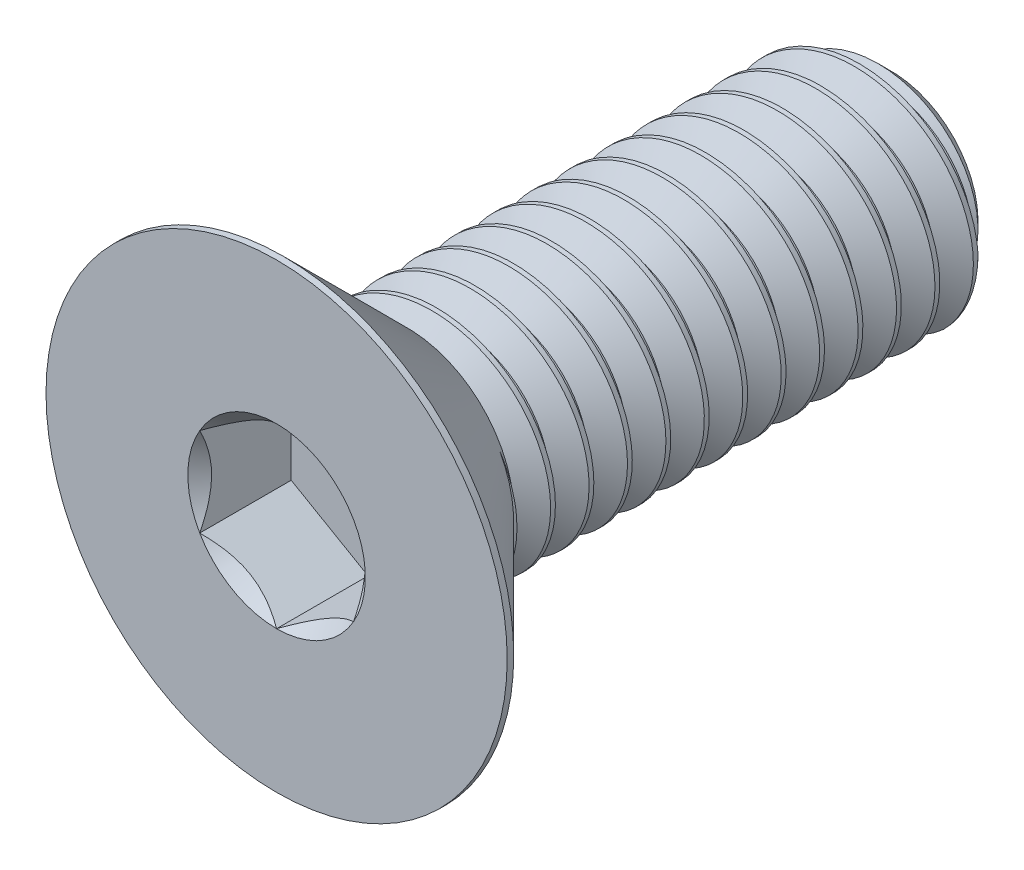
SolidWorks part; units mm, degrees
ref_plane "Front" through (0, 0, 0) normal (0, 0, 1) x (1, 0, 0)
ref_plane "Top" through (0, 0, 0) normal (0, 1, 0) x (1, 0, 0)
ref_plane "Right" through (0, 0, 0) normal (1, 0, 0) x (0, 0, -1)
sketch "Sketch11" plane through (0, 0, 0) normal (1, 0, 0) x (0, 0, -1)
  line L0 (-4, 3) -> (4, 3) construction
  line L5 (-4, 3) -> (-4, -3) construction
  line L6 (4, 1.5) -> (4, -1.5) construction
  line L7 (-3.99, 1) -> (-3.99, -1) construction
  line L8 (3.9688, 1.5541) -> (4.4688, 1.5541) construction
  line L9 (4.4688, 1.5541) -> (4.2188, 1.1211) construction
  line L10 (4.2188, 1.1211) -> (3.9688, 1.5541) construction
  line L11 (4.1875, 1.1752) -> (4.25, 1.1752) construction
  line L12 (4.2188, 1.1752) -> (4.2188, 1.1211) construction
  line L13 (3.9844, 1.5271) -> (4.4531, 1.5271) construction
  line L14 (4.2188, 1.5541) -> (4.2188, 1.5) construction
  line L15 (4, 1.5) -> (4.4375, 1.5) construction
  line L17 (-3.915, 3) -> (-0.915, 0) construction
  line L18 (-0.915, 0) -> (-3.915, -3) construction
  point P3 (-2.3, 3)
  point P8 (0, 3)
  point P21 (4.2188, 1.5271)
  point P26 (-4, 0)
  point P28 (-3.99, 0)
  point P29 (4, 0)
  dimension "Length" = 8
  dimension "Head Diameter" = 6
  dimension "Thread Major Diameter" = 3
  dimension "Head Height" = 1.7
  dimension "Drive Size" = 2
  dimension "Thread Pitch" = 0.5
  dimension "D1" = 0.0625
  dimension "D2" = 0.01
  dimension "D3" = 0.085
  dimension "Countersink Angle" = 90
sketch "Sketch1" plane through (0, 0, 0) normal (1, 0, 0) x (0, 0, -1)
  line L2 (-2.3, 1.5) -> (4, 1.5)
  line L3 (4, 1.5) -> (4, 0)
  line L4 (-2.81, 1.5) -> (-2.81, 0)
  line L5 (-2.3, 1.5) -> (-2.81, 1.5)
  line L6 (-4, 3) -> (-4, -3) construction
  line L7 (4, 1.5) -> (4, -1.5) construction
  line L8 (-2.81, 0) -> (4, 0)
  dimension "D1" = 1.19
revolve "Revolve1" add sketch "Sketch1" angle 360 mid plane about L8
chamfer "Chamfer1" distance 0.375 angle 45 1 edges at (0, -1.5, -4)
sketch "Sketch7" plane through (0, 0, 0) normal (1, 0, 0) x (0, 0, -1)
  line L2 (-4, 3) -> (-3.915, 3)
  line L5 (-2.3, 1.385) -> (-2.3, 0)
  line L6 (-4, 3) -> (-4, 0)
  line L8 (-4, 3) -> (-4, -3) construction
  line L9 (-4, 0) -> (-2.3, 0)
  line L12 (-3.915, 3) -> (-2.3, 1.385)
  line L13 (-3.915, 3) -> (-0.915, 0) construction
revolve "Revolve2" add sketch "Sketch7" angle 360 mid plane about L9 region at (0, 1.1696, 3.2571)
ref_plane "Plane1" through (0, 0, 2.3) normal (0, 0, 1) x (1, 0, 0)
sketch "Sketch5" plane through (0, 0, 4) normal (0, 0, 1) x (1, 0, 0)
  line L1 (1, -0.5774) -> (1, 0.5774)
  line L2 (1, 0.5774) -> (0, 1.1547)
  line L3 (0, 1.1547) -> (-1, 0.5774)
  line L4 (-1, 0.5774) -> (-1, -0.5774)
  line L5 (-1, -0.5774) -> (0, -1.1547)
  line L6 (0, -1.1547) -> (1, -0.5774)
  circle A0 centre (0, 0) radius 1 construction
extrude "Cut-Extrude2" cut sketch "Sketch5" against normal blind 1.19
sketch "Sketch6" plane through (0, 0, 4) normal (0, 0, -1) x (-1, 0, 0)
  circle A0 centre (0, 0) radius 1.1547
extrude "Cut-Extrude3" cut sketch "Sketch6" along normal blind 1.19 draft 45
sketch "Sketch12" plane through (0, 0, -4) normal (0, 0, -1) x (-1, 0, 0)
  circle A0 centre (0, 0) radius 1.5 construction
  circle A1 centre (0, 0) radius 1.5
curve "Helix/Spiral1" pitch 0.5 height 8 radius 1.5 centre (0, 0, -4) axis (0, 0, 1) start towards (0, 1, 0)
sketch "Sketch13" plane through (0, 0, 0) normal (1, 0, 0) x (0, 0, -1)
  line L0 (3.9844, 1.5271) -> (4.4531, 1.5271)
  line L1 (4.4531, 1.5271) -> (4.25, 1.1752)
  line L2 (4.25, 1.1752) -> (4.1875, 1.1752)
  line L3 (4.1875, 1.1752) -> (3.9844, 1.5271)
sweep "Cut-Sweep1" cut profiles "Sketch13" path "Helix/Spiral1" align with end faces yes
combine bodies "Combine1" operation type add bodies to combine 113 127
equation "\"D1@Chamfer1\"=\"Thread Pitch@Sketch11\" * .75"
equation "\"D1@Cut-Extrude2\"= \"Head Height@Sketch11\" * .7"
equation "\"D1@Cut-Extrude3\" = \"D1@Cut-Extrude2\""
equation "\"D1@Sketch11\"=\"Thread Pitch@Sketch11\"/8"
equation "\"D3@Sketch11\"=\"Head Height@Sketch11\"*.05"
equation "\"D4@Helix/Spiral1\"=\"Thread Pitch@Sketch11\""
equation "\"D1@Sketch1\"=\"Head Height@Sketch11\"*.7"
equation "\"D3@Helix/Spiral1\"=\"Length@Sketch11\""
